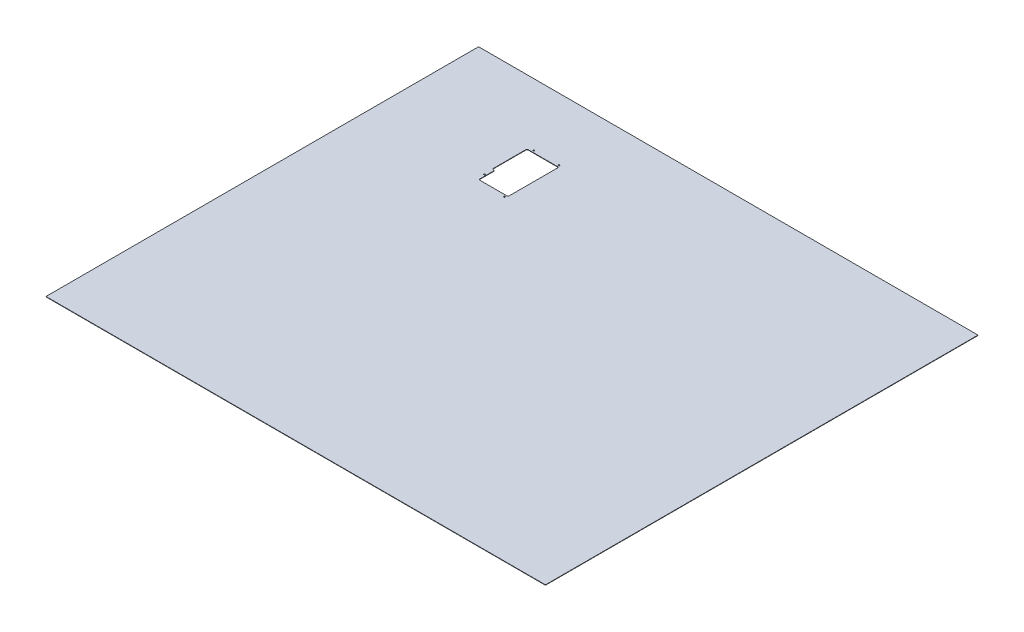
SolidWorks part; units mm, degrees
ref_plane "Front Plane" through (0, 0, 0) normal (0, 0, 1) x (1, 0, 0)
ref_plane "Top Plane" through (0, 0, 0) normal (0, 1, 0) x (1, 0, 0)
ref_plane "Right Plane" through (0, 0, 0) normal (1, 0, 0) x (0, 0, -1)
sketch "Sketch1" plane through (0, 0, 0) normal (0, 1, 0) x (1, 0, 0)
  line L1 (-631, 546.5) -> (631, 546.5)
  line L2 (-631, 546.5) -> (-631, -546.5)
  line L3 (-631, -546.5) -> (631, -546.5)
  line L4 (631, 546.5) -> (631, -546.5)
  line L5 (-631, 546.5) -> (631, -546.5) construction
  line L6 (-631, -546.5) -> (631, 546.5) construction
  point P0 (0, 0)
  dimension "D1" = 1262
  dimension "D2" = 1093
extrude "Boss-Extrude1" add sketch "Sketch1" along normal blind 1
sketch "Sketch2" plane through (0, 1, 0) normal (0, 1, 0) x (1, 0, 0)
  line L0 (631, 546.5) -> (-631, 546.5) construction
  line L1 (-266, 256) -> (-346, 256)
  line L2 (-266, 256) -> (-266, 384)
  line L3 (-266, 384) -> (-346, 384)
  line L4 (-346, 256) -> (-346, 384)
  line L5 (-631, 546.5) -> (-631, -546.5) construction
  line L7 (-346, 256) -> (-340, 256)
  line L8 (-346, 256) -> (-346, 296)
  line L9 (-346, 296) -> (-340, 296)
  line L10 (-340, 256) -> (-340, 296)
  dimension "D1" = 128
  dimension "D2" = 80
  dimension "D3" = 162.5
  dimension "D4" = 285
  dimension "D5" = 40
  dimension "D6" = 6
extrude "Cut-Extrude1" cut sketch "Sketch2" against normal blind 10 contours L10 L1 L2 L3 L4 L9 region at (-305.112, 1, -321.056)
fillet "Fillet2" radius 3 6 edges at (-266, 0.5, -256) (-340, 0.5, -256) (-340, 0.5, -296) (-346, 0.5, -296) (-346, 0.5, -384) (-266, 0.5, -384)
sketch "Sketch3" plane through (0, 1, 0) normal (0, 1, 0) x (1, 0, 0)
  line L0 (-269, 384) -> (-343, 384) construction
  line L1 (-340, 259) -> (-340, 293) construction
  line L2 (-269, 256) -> (-337, 256) construction
  line L3 (-346, 299) -> (-346, 381) construction
  line L4 (-266, 259) -> (-266, 381) construction
  circle A0 centre (-270, 389) radius 1.75
  circle A1 centre (-334, 389) radius 1.75
  circle A2 centre (-344, 275) radius 1.75
  circle A3 centre (-270, 251) radius 1.75
  dimension "D1" = 3.5
  dimension "D2" = 3.5
  dimension "D3" = 3.5
  dimension "D4" = 3.5
  dimension "D5" = 5
  dimension "D6" = 5
  dimension "D7" = 4
  dimension "D8" = 5
  dimension "D9" = 12
  dimension "D10" = 4
  dimension "D11" = 19
  dimension "D12" = 4
extrude "Cut-Extrude2" cut sketch "Sketch3" against normal blind 10
